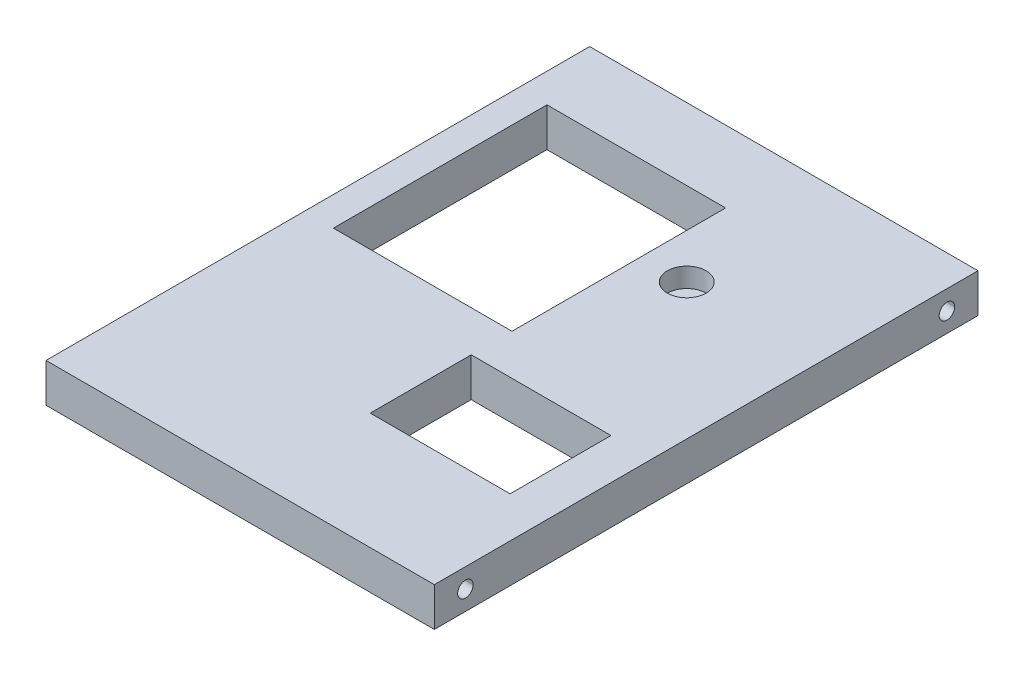
SolidWorks part; units mm, degrees
material "Acrylic (Medium-high impact)"
ref_plane "Front Plane" through (0, 0, 0) normal (0, 0, 1) x (1, 0, 0)
ref_plane "Top Plane" through (0, 0, 0) normal (0, 1, 0) x (1, 0, 0)
ref_plane "Right Plane" through (0, 0, 0) normal (1, 0, 0) x (0, 0, -1)
sketch "Sketch2" plane through (0, 0, 0) normal (0, 1, 0) x (1, 0, 0)
  line L0 (0, 0) -> (0, 140)
  line L1 (0, 140) -> (100, 140)
  line L2 (100, 140) -> (100, 0)
  line L3 (100, 0) -> (0, 0)
  dimension "D1" = 100
  dimension "D2" = 140
extrude "Boss-Extrude1" add sketch "Sketch2" along normal blind 10
sketch "Sketch3" plane through (0, 10, 0) normal (0, 1, 0) x (1, 0, 0)
  line L0 (100, 0) -> (100, 140) construction
  circle A0 centre (65, 100) radius 5
  dimension "D2" = 10
  dimension "D1" = 35
extrude "MountHole" cut sketch "Sketch3" against normal blind 5
sketch "Sketch4" plane through (0, 0, 0) normal (-1, 0, 0) x (0, 0, 1)
  line L0 (-8, 10) -> (-8, 0) construction
  line L1 (-140, 10) -> (0, 10) construction
  line L2 (-140, 0) -> (0, 0) construction
  line L3 (0, 10) -> (0, 0) construction
  circle A0 centre (-8, 5) radius 2
  dimension "D2" = 4
  dimension "D1" = 8
extrude "Cut-Extrude2" cut sketch "Sketch4" against normal through all
sketch "Sketch5" plane through (0, 0, 0) normal (-1, 0, 0) x (0, 0, 1)
  line L0 (-132, 10) -> (-132, 0) construction
  line L1 (-140, 10) -> (0, 10) construction
  line L2 (-140, 0) -> (0, 0) construction
  line L3 (-140, 10) -> (-140, 0) construction
  circle A0 centre (-132, 5) radius 2
  dimension "D2" = 4
  dimension "D1" = 8
extrude "Cut-Extrude3" cut sketch "Sketch5" against normal through all
fillet "Fillet1" [suppressed] radius 2
fillet "Fillet4" [suppressed] radius 0.5
fillet "Fillet6" [suppressed] radius 0.5
sketch "Sketch7" plane through (0, 10, 0) normal (0, 1, 0) x (1, 0, 0)
  line L0 (11, 0) -> (11, 43) construction
  line L1 (0, 0) -> (100, 0) construction
  line L2 (0, 140) -> (0, 0) construction
  line L3 (11, 43) -> (47.1706, 43) construction
  line L9 (11, 43) -> (-5.1328, 43) construction
  line L15 (2.5, 56) -> (2.5, 30)
  line L16 (2.5, 56) -> (30.5, 56)
  line L17 (30.5, 56) -> (30.5, 30)
  line L18 (30.5, 30) -> (2.5, 30)
  point P10 (2.5, 43)
  dimension "D1" = 43
  dimension "D2" = 11
  dimension "D3" = 26
  dimension "D4" = 28
  dimension "D5" = 8.5
extrude "Boss-Extrude2" [suppressed] add sketch "Sketch7" along normal blind 4
sketch "Sketch21" plane through (0, 10, 0) normal (0, 1, 0) x (1, 0, 0)
  line L5 (7.5, 121.5) -> (53.5, 121.5)
  line L6 (7.5, 121.5) -> (7.5, 66.5)
  line L7 (7.5, 66.5) -> (53.5, 66.5)
  line L8 (53.5, 121.5) -> (53.5, 66.5)
  line L9 (7.5, 121.5) -> (53.5, 66.5) construction
  line L10 (7.5, 66.5) -> (53.5, 121.5) construction
  line L15 (53.5, 56) -> (53.5, 30)
  line L20 (53.5, 30) -> (89.5, 30)
  line L21 (89.5, 30) -> (89.5, 56)
  line L22 (89.5, 56) -> (53.5, 56)
  point P0 (30.5, 94)
  dimension "D1" = 46
  dimension "D2" = 55
  dimension "D5" = 36
extrude "Cut-Extrude10" cut sketch "Sketch21" against normal through all
sketch "Sketch10" [suppressed] plane through (0, 14, 0) normal (0, 1, 0) x (1, 0, 0)
  line L0 (2.5, 56) -> (2.5, 30)
  line L1 (2.5, 30) -> (3.5, 30)
  line L2 (2.5, 30) -> (30.5, 30) construction
  line L3 (3.5, 30) -> (3.5, 56)
  line L4 (30.5, 56) -> (2.5, 56) construction
  line L5 (3.5, 56) -> (2.5, 56)
  dimension "D1" = 1
extrude "Boss-Extrude3" [suppressed] add sketch "Sketch10" along normal blind 24
sketch "Sketch13" [suppressed] plane through (2.5, 0, 0) normal (-1, 0, 0) x (0, 0, 1)
  line L0 (-43, 10) -> (-43, 22.354) construction
  line L1 (-56, 10) -> (-30, 10) construction
  line L2 (-43, 22.354) -> (-38.75, 29.7152) construction
  line L3 (-43, 22.354) -> (-6.4369, 22.354) construction
  line L4 (-43, 22.354) -> (-47.25, 29.7152) construction
  circle A0 centre (-43, 22.354) radius 3
  circle A1 centre (-38.75, 29.7152) radius 1
  circle A2 centre (-47.25, 29.7152) radius 1
  dimension "D2" = 6
  dimension "D5" = 2
  dimension "D8" = 2
  dimension "D1" = 12.354
  dimension "D3" = 60
  dimension "D4" = 8.5
  dimension "D6" = 120
  dimension "D7" = 8.5
extrude "Cut-Extrude6" [suppressed] cut sketch "Sketch13" against normal up to surface (1 mm away)
sketch "Sketch20" [suppressed] plane through (30.5, 0, 0) normal (1, 0, 0) x (0, 0, -1)
  line L0 (43, 10) -> (43, 39.7821) construction
  line L2 (30, 10) -> (56, 10) construction
  line L3 (30, 14) -> (56, 14) construction
  line L4 (30, 14) -> (56, 14) construction
  line L5 (30, 14) -> (34.5198, 14)
  line L6 (51.4802, 14) -> (56, 14)
  arc A0 (34.5198, 14) -> (51.4802, 14) centre (43, 22.4904) ccw
  dimension "D1" = 12
extrude "Cut-Extrude9" [suppressed] cut sketch "Sketch20" against normal blind 27 and the other way through all
sketch "Sketch22" plane through (100, 0, 0) normal (1, 0, 0) x (0, 0, -1)
  line L0 (6, 5) -> (10, 5)
  line L1 (130, 5) -> (134, 5)
  circle A0 centre (8, 5) radius 2 construction
  circle A1 centre (132, 5) radius 2 construction
split line "Split Line1"
split line "Split Line2"
sketch "Sketch22<2>" plane through (100, 0, 0) normal (1, 0, 0) x (0, 0, -1) same geometry as "Sketch22"
